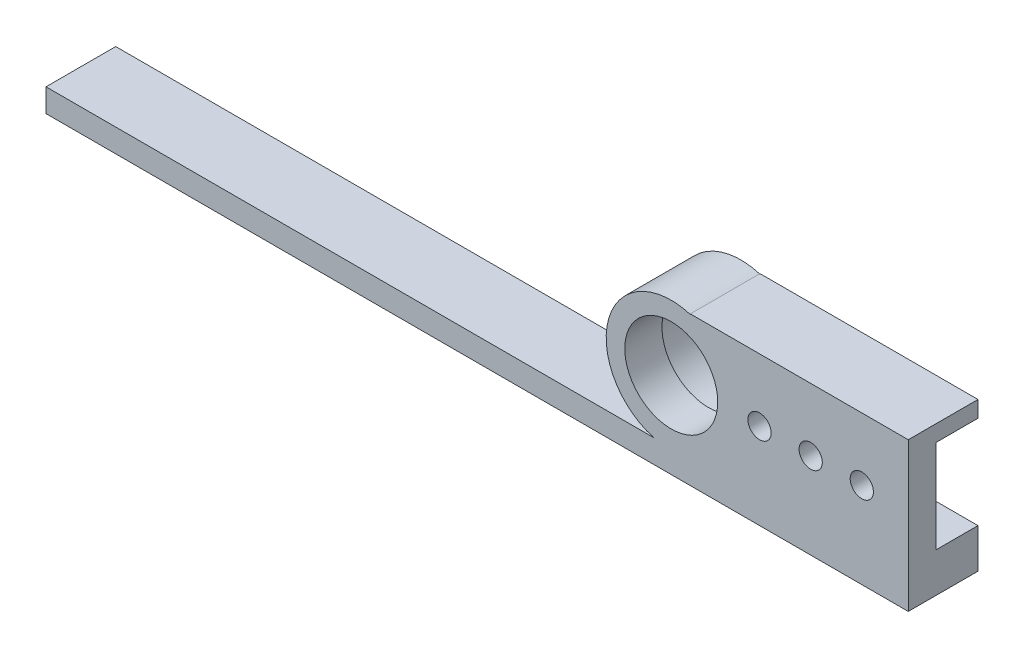
SolidWorks part; units mm, degrees
ref_plane "前视基准面" through (0, 0, 0) normal (0, 0, 1) x (1, 0, 0)
ref_plane "上视基准面" through (0, 0, 0) normal (0, 1, 0) x (1, 0, 0)
ref_plane "右视基准面" through (0, 0, 0) normal (1, 0, 0) x (0, 0, -1)
sketch "草图1" plane through (0, 0, 0) normal (0, 0, 1) x (1, 0, 0)
  line L1 (20, -10) -> (-20, -10)
  line L2 (20, -10) -> (20, 10)
  line L3 (20, 10) -> (-20, 10)
  line L4 (-20, -10) -> (-20, 10)
  line L5 (20, -10) -> (-20, 10) construction
  line L6 (20, 10) -> (-20, -10) construction
  point P0 (0, 0)
  dimension "D1" = 40
  dimension "D2" = 20
extrude "凸台-拉伸1" add sketch "草图1" along normal blind 6
sketch "草图2" plane through (0, 0, 6) normal (0, 0, 1) x (1, 0, 0)
  line L0 (20, -10) -> (20, 10) construction
  circle A0 centre (10, 0) radius 2.5
  circle A1 centre (-1, 0) radius 2.5
  circle A2 centre (-12, 0) radius 2.5
  dimension "D1" = 10
  dimension "D2" = 5
  dimension "D3" = 3
extrude "切除-拉伸1" cut sketch "草图2" against normal through all
sketch "草图3" plane through (0, 0, 6) normal (0, 0, 1) x (1, 0, 0)
  line L0 (20, 13.5) -> (20, 10)
  line L1 (20, -13.5) -> (-26.894, -13.5)
  line L3 (20, 13.5) -> (-26.894, 13.5)
  line L4 (-20, 10) -> (-20, -10)
  line L5 (-20, -10) -> (20, -10)
  line L6 (20, -10) -> (20, 10)
  line L7 (20, 10) -> (-20, 10)
  line L8 (-20, 10) -> (-20, -10)
  line L9 (-20, -10) -> (20, -10)
  line L10 (20, -10) -> (20, 10)
  line L11 (20, 10) -> (-20, 10)
  line L12 (-26.894, -13.5) -> (-26.894, 13.5)
  line L13 (20, -10.0394) -> (-26.894, 13.5) construction
  line L14 (20, 10.0394) -> (-26.894, -13.5) construction
  line L15 (20, -10) -> (20, -13.5)
  circle A0 centre (-31, 0) radius 11
  circle A1 centre (-31, 0) radius 14
  point P2 (0, 0)
  line M10 (-20, 10) -> (-20, -10)
  line M11 (-20, -10) -> (20, -10)
  line M13 (20, 10) -> (-20, 10)
  dimension "D3" = 22
  dimension "D4" = 28
  dimension "D2" = 3.5
  dimension "D1" = 0
extrude "凸台-拉伸2" add sketch "草图3" against normal blind 15 contours L3 A1 L1 L12 A0 | A1 L1 L15 M11 M10 | L1 A1 L8 A0 L12 | L8 A1 L3 L12 A0 | L8 A1 | A1 L0 L3 M10 M13 region at (-1.9449, 11.7771, 6) region at (-1.9449, -11.7771, 6) region at (-23.0173, 9.0328, 6) region at (-27.2274, 11.7946, 6) region at (-18.7882, 0, 6) region at (-23.0173, -9.0328, 6)
sketch "草图5" plane through (0, 0, 6) normal (0, 0, 1) x (1, 0, 0)
  circle A0 centre (-31, 0) radius 10
  circle A1 centre (-31, 0) radius 11 construction
  circle A2 centre (-31, 0) radius 11
  dimension "D1" = 20
extrude "凸台-拉伸3" add sketch "草图5" against normal blind 8
sketch "草图6" plane through (0, 0, 6) normal (0, 0, 1) x (1, 0, 0)
  circle A0 centre (-31, 0) radius 8.5
  circle A1 centre (-31, 0) radius 10 construction
  circle A2 centre (-31, 0) radius 10
  dimension "D1" = 17
sketch "草图8" plane through (0, 0, 6) normal (0, 0, 1) x (1, 0, 0)
  line L0 (20, -13.5) -> (20, 13.5) construction
  line L1 (20, -13.5) -> (-26.894, -13.5) construction
  line L2 (20, 13.5) -> (-26.894, 13.5) construction
  line L3 (20, -13.5) -> (20, 13.5)
  line L4 (20, -13.5) -> (-26.894, -13.5)
  line L5 (20, 13.5) -> (-26.894, 13.5)
  line L6 (-45, -14) -> (-26.894, -13.5)
  line L7 (-45, -14) -> (-239, -14)
  line L8 (-45, -14) -> (-45, 14)
  line L9 (-45, 14) -> (-239, 14)
  line L10 (-239, -14) -> (-239, 14)
  line L11 (-45, -14) -> (-239, 14) construction
  line L12 (-45, 14) -> (-239, -14) construction
  line L13 (-45, 14) -> (-26.894, 13.3843)
  line L14 (-12, 0) -> (-31, 0)
  arc A0 (-26.894, 13.3843) -> (-26.894, -13.3843) centre (-31, 0) ccw construction
  arc A1 (-26.894, 13.3843) -> (-26.894, -13.3843) centre (-31, 0) ccw
  point P6 (-142, 0)
  dimension "D1" = 28
  dimension "D2" = 194
  dimension "D3" = 14
sketch "草图9" plane through (0, -13.5, 0) normal (0, -1, 0) x (1, 0, 0)
  circle A0 centre (10.5344, 0) radius 5.2388
sketch "草图10" plane through (20, 0, 0) normal (1, 0, 0) x (0, 0, -1)
  line L1 (9, -13.5) -> (-6, -13.5)
  line L2 (9, -13.5) -> (9, -18.5)
  line L3 (9, -18.5) -> (-6, -18.5)
  line L4 (-6, -13.5) -> (-6, -18.5)
  dimension "D1" = 5
extrude "凸台-拉伸4" add sketch "草图10" against normal blind 500
sketch "草图11" plane through (0, 0, -9) normal (0, 0, -1) x (-1, 0, 0)
  line L1 (22.0371, -11.3638) -> (33.5283, -11.3638)
  line L2 (22.0371, -11.3638) -> (22.0371, -16.4864)
  line L3 (22.0371, -16.4864) -> (33.5283, -16.4864)
  line L4 (33.5283, -11.3638) -> (33.5283, -16.4864)
extrude "凸台-拉伸5" add sketch "草图11" against normal through all
sketch "草图12" plane through (0, -18.5, 0) normal (0, -1, 0) x (1, 0, 0)
  line L0 (-165.5205, -220.2089) -> (-165.5205, 6)
  line L1 (-165.5205, 19.2909) -> (-165.5205, -350.7091) construction
  line L2 (-165.5205, -220.2089) -> (-39.8292, -220.2089) construction
  line L3 (-480, 6) -> (20, 6) construction
sketch "草图13" plane through (0, -18.5, 0) normal (0, -1, 0) x (1, 0, 0)
  line L1 (-165.5205, -220.2089) -> (-490.0472, -220.2089)
  line L2 (-165.5205, -220.2089) -> (-165.5205, 14.9475)
  line L3 (-165.5205, 14.9475) -> (-490.0472, 14.9475)
  line L4 (-490.0472, -220.2089) -> (-490.0472, 14.9475)
extrude "切除-拉伸2" cut sketch "草图13" against normal through all
sketch "草图14" plane through (-480, 0, 0) normal (-1, 0, 0) x (0, 0, 1)
  line L4 (-6.8295, -18.5) -> (-6.8295, -13.5)
  line L5 (-6.8295, -13.5) -> (-9, -13.5)
  line L6 (-9, -13.5) -> (-9, -18.5)
  line L7 (-9, -18.5) -> (-6.8295, -18.5)
  line L8 (-6.8295, -18.5) -> (-6.8295, -13.5)
  line L9 (-6.8295, -13.5) -> (-9, -13.5)
  line L10 (-9, -13.5) -> (-9, -18.5)
  line L11 (-9, -18.5) -> (-6.8295, -18.5)
  dimension "D1" = 0
extrude "切除-拉伸3" cut sketch "草图14" against normal up to surface (314.4795 mm away) rebuild error yes up to face at (-165.5205, -16, -1.5)
